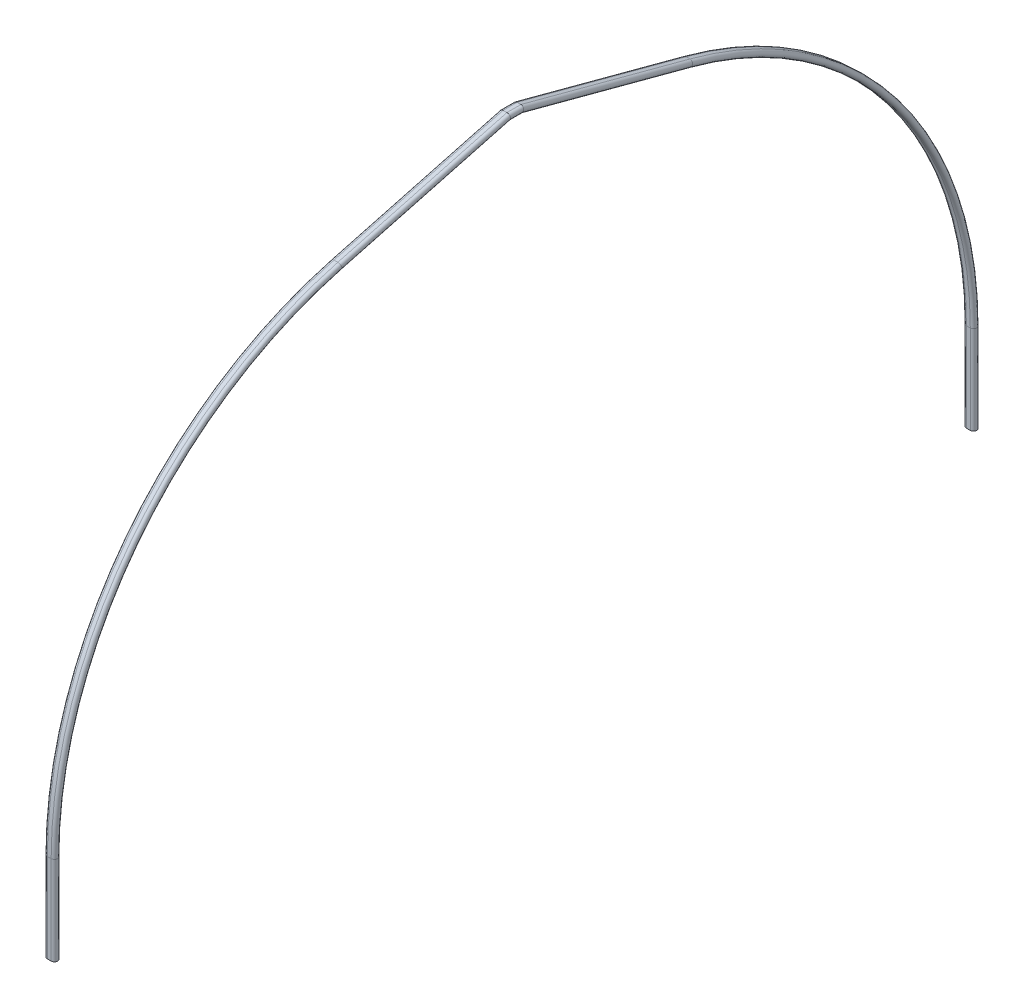
SolidWorks part; units mm, degrees
ref_plane "Front Plane" through (0, 0, 0) normal (0, 0, 1) x (1, 0, 0)
ref_plane "Top Plane" through (0, 0, 0) normal (0, 1, 0) x (1, 0, 0)
ref_plane "Right Plane" through (0, 0, 0) normal (1, 0, 0) x (0, 0, -1)
sketch "Sketch1" plane through (0, 0, 0) normal (0, 1, 0) x (1, 0, 0)
  line L0 (0, 0) -> (38.1, 0) construction
  line L1 (0, 31.75) -> (38.1, 31.75)
  line L2 (0, -31.75) -> (38.1, -31.75)
  line L3 (0, 0) -> (38.1, 0) construction
  line L4 (0, 20.3048) -> (38.1, 20.3048)
  line L5 (0, -20.3048) -> (38.1, -20.3048)
  arc A0 (0, 31.75) -> (0, -31.75) centre (0, 0) ccw
  arc A1 (38.1, -31.75) -> (38.1, 31.75) centre (38.1, 0) ccw
  arc A2 (0, 20.3048) -> (0, -20.3048) centre (0, 0) ccw
  arc A3 (38.1, -20.3048) -> (38.1, 20.3048) centre (38.1, 0) ccw
  point P3 (19.05, 0)
  point P10 (19.05, 0)
  dimension "D1" = 38.1
  dimension "D2" = 63.5
sketch "Sketch4" plane through (0, 0, 0) normal (1, 0, 0) x (0, 0, -1)
  line L0 (0, 0) -> (0, 882.8596)
  line L1 (6315.6947, 4564.2147) -> (4637.4463, 5011.7476)
  line L2 (0, 0) -> (4572, 0) construction
  line L3 (4572, 0) -> (4572, 5029.2) construction
  line L4 (2828.3053, 4564.2147) -> (4506.5537, 5011.7476)
  line L5 (9144, 0) -> (9144, 882.8596)
  line L6 (0, 3810) -> (7772.8418, 3810) construction
  line L7 (4506.5537, 5011.7476) -> (4637.4463, 5011.7476)
  arc A0 (0, 882.8596) -> (2828.3053, 4564.2147) centre (3810, 882.8596) cw
  arc A1 (9144, 882.8596) -> (6315.6947, 4564.2147) centre (5334, 882.8596) ccw
  point P3 (0, 0)
  point P8 (0, 3810)
  dimension "D2" = 4572
  dimension "D4" = 3810
  dimension "D1" = 3810
  dimension "D3" = 5029.2
sweep "Sweep1" add profiles "Sketch1" path "Sketch4"
sketch3d "3DSketch8"
  line L0 (0, 4979.9976, -4633.2857) -> (0, 4979.9976, -4510.7143) construction
  line L1 (38.1, 4979.9976, -4633.2857) -> (38.1, 4979.9976, -4510.7143) construction
  line L2 (0, 4979.9976, -4572) -> (0, 4979.9976, -4552.95)
  line L3 (0, 4979.9976, -4572) -> (0, 4979.9976, -4591.05)
  line L4 (38.1, 4979.9976, -4572) -> (38.1, 4979.9976, -4591.05)
  line L5 (38.1, 4979.9976, -4572) -> (38.1, 4979.9976, -4552.95)
  line L6 (19.05, 4979.9976, -4510.7143) -> (19.05, 4979.9976, -4633.2857) construction
  line L7 (0, 4979.9976, -4510.7143) -> (38.1, 4979.9976, -4510.7143) construction
  line L8 (0, 4979.9976, -4633.2857) -> (38.1, 4979.9976, -4633.2857) construction
  circle A0 centre (0, 4979.9976, -4552.95) radius 6.35
  circle A1 centre (0, 4979.9976, -4591.05) radius 6.35
  circle A2 centre (38.1, 4979.9976, -4591.05) radius 6.35
  circle A3 centre (38.1, 4979.9976, -4552.95) radius 6.35
  point P0 (18.6117, 4979.9976, -4560.4976)
  point P12 (0, 4986.3476, -4552.95)
  point P15 (0, 4986.3476, -4591.05)
  point P20 (38.1, 4986.3476, -4591.05)
  point P22 (38.1, 4986.3476, -4552.95)
  dimension "D2" = 12.7
  dimension "D4" = 12.7
  dimension "D7" = 12.7
  dimension "D8" = 12.7
  dimension "D1" = 19.05
  dimension "D3" = 19.05
  dimension "D5" = 19.05
  dimension "D6" = 19.05
ref_plane "Plane10" through (0, 4979.9976, 0) normal (0, -1, 0) x (1, 0, 0)
extrude "Cut-Extrude1" cut sketch "3DSketch8" along direction (0, 1, 0) on the side of the normal blind 25.4 contours A3 | A0 | A1 | A2
